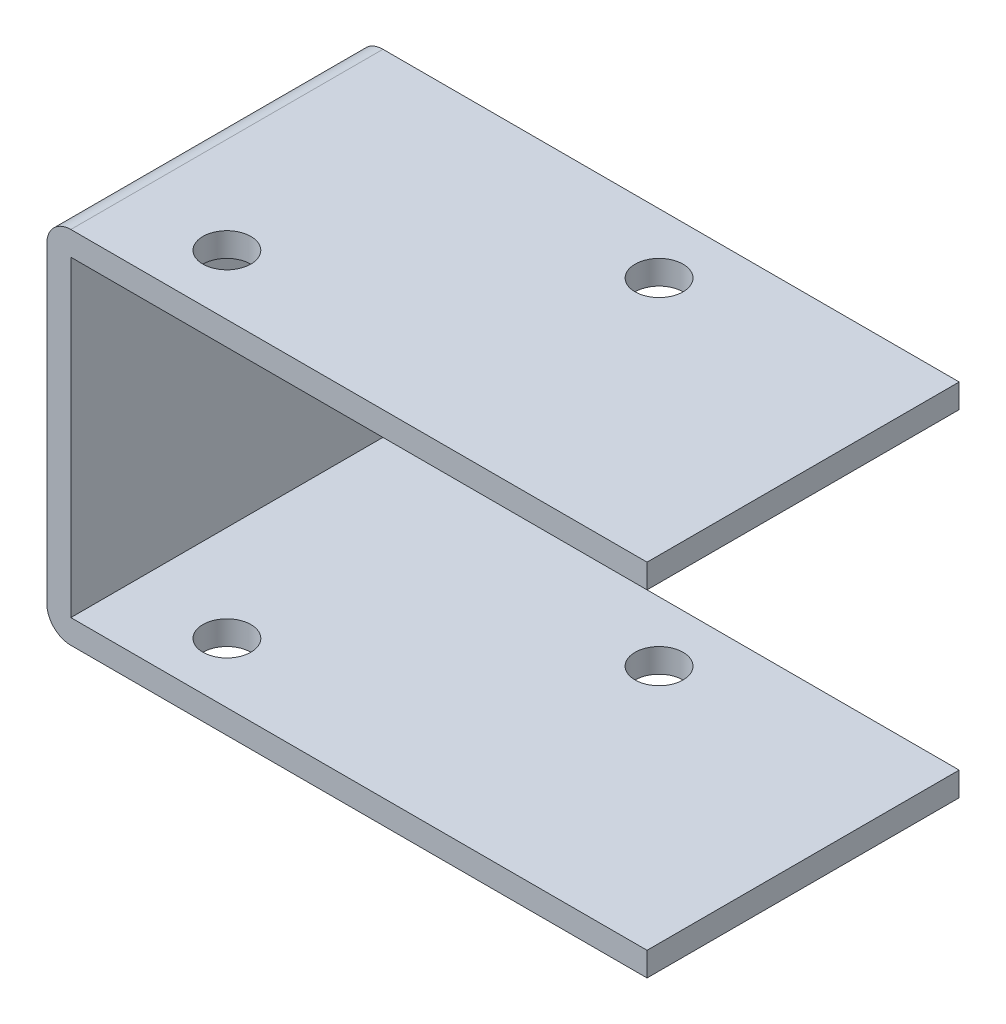
SolidWorks part; units mm, degrees
ref_plane "Front Plane" through (0, 0, 0) normal (0, 0, 1) x (1, 0, 0)
ref_plane "Top Plane" through (0, 0, 0) normal (0, 1, 0) x (1, 0, 0)
ref_plane "Right Plane" through (0, 0, 0) normal (1, 0, 0) x (0, 0, -1)
sketch "Sketch2" plane through (0, 0, 0) normal (0, 0, 1) x (1, 0, 0)
  line L0 (0, 0) -> (0, -1)
  line L1 (-24, -14) -> (0, -14)
  line L2 (-24, -1) -> (0, -1)
  line L3 (0, 0) -> (-24, 0)
  line L4 (-25, -1) -> (-25, -14)
  line L5 (-24, -1) -> (-24, -14)
  line L6 (0, -14) -> (0, -15)
  line L7 (0, -15) -> (-24, -15)
  arc A0 (-24, 0) -> (-25, -1) centre (-24, -1) ccw
  arc A1 (-24, -15) -> (-25, -14) centre (-24, -14) cw
  dimension "D1" = 1
  dimension "D2" = 24
  dimension "D4" = 13
extrude "Boss-Extrude1" add sketch "Sketch2" along normal blind 13 contours A1 L7 L6 L1 L5 L2 L0 L3 A0 L4 region at (-0.2915, -0.5, 0)
sketch "Sketch3" plane through (0, 0, 0) normal (0, 1, 0) x (1, 0, 0)
  line L0 (0, 0) -> (-24, 0) construction
  line L2 (-25, -13) -> (-25, 0) construction
  circle A0 centre (-10, -2.5) radius 1
  circle A1 centre (-20, -10.5) radius 1
  dimension "D5" = 2
  dimension "D6" = 2
  dimension "D1" = 8
  dimension "D2" = 2.5
  dimension "D3" = 5
  dimension "D4" = 10
extrude "Cut-Extrude1" cut sketch "Sketch3" against normal through all both and the other way through all contours A0
extrude "Cut-Extrude2" cut sketch "Sketch3<4>" against normal through all both
sketch "Sketch3<4>" plane through (0, 0, 0) normal (0, 1, 0) x (1, 0, 0) same geometry as "Sketch3"
